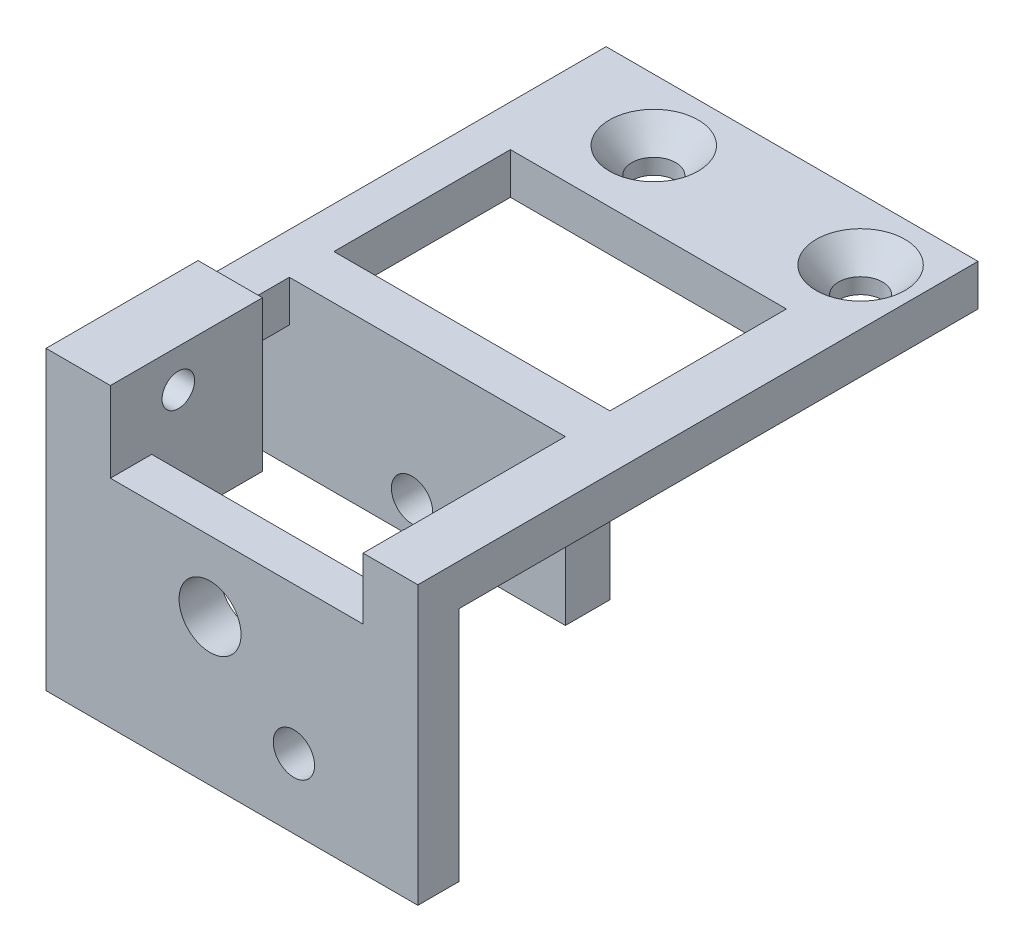
SolidWorks part; units mm, degrees
material "ABS"
ref_plane "Front Plane" through (0, 0, 0) normal (0, 0, 1) x (1, 0, 0)
ref_plane "Top Plane" through (0, 0, 0) normal (0, 1, 0) x (1, 0, 0)
ref_plane "Right Plane" through (0, 0, 0) normal (1, 0, 0) x (0, 0, -1)
sketch "Sketch1" plane through (0, 0, 0) normal (0, 0, 1) x (1, 0, 0)
  line L0 (0, 8.8442) -> (12.8921, -2.9343) construction
  line L1 (23.5226, 29.0697) -> (31.9421, 29.0697)
  line L2 (-25.2079, 8.8442) -> (-25.2079, -13.6023)
  line L3 (-25.2079, -13.6023) -> (31.9421, -13.6023)
  line L4 (31.9421, 29.0697) -> (31.9421, -13.6023)
  line L6 (-25.2079, 8.8442) -> (-25.2079, 31.9582)
  line L7 (-25.2079, 31.9582) -> (-18.8579, 31.9582)
  line L11 (23.5226, 22.6565) -> (23.5226, 29.0697)
  line L12 (-18.8579, 31.9582) -> (-15.3109, 31.9582)
  line L14 (-15.3109, 31.9582) -> (-15.3109, 22.6565)
  line L15 (-15.3109, 22.6565) -> (-15.3109, 19.6203)
  line L16 (-15.3109, 19.6203) -> (23.5226, 19.6203)
  line L17 (23.5226, 19.6203) -> (23.5226, 22.6565)
  circle A0 centre (12.8921, -2.9343) radius 3.175
  circle A1 centre (0, 8.8442) radius 4.7625
  dimension "D5" = 9.525
  dimension "D9" = 6.35
  dimension "D1" = 23.114
  dimension "D2" = 57.15
  dimension "D3" = 42.672
  dimension "D4" = 6.35
  dimension "D6" = 19.05
  dimension "D7" = 10.668
  dimension "D8" = 17.4625
extrude "Boss-Extrude1" add sketch "Sketch1" against normal blind 6.35
sketch "Sketch2" plane through (0, 0, 0) normal (0, 0, 1) x (1, 0, 0)
  line L0 (-25.2079, 31.9582) -> (-25.2079, -13.6023) construction
  line L1 (-18.8579, 31.9582) -> (-25.2079, 31.9582)
  line L3 (-18.8579, 8.8442) -> (-25.2079, 8.8442)
  line L4 (-25.2079, 31.9582) -> (-25.2079, 8.8442)
  line L6 (-15.3109, 31.9582) -> (-25.2079, 31.9582)
  line L7 (-15.3109, 31.9582) -> (-15.3109, 8.8442)
  line L8 (-15.3109, 8.8442) -> (-25.2079, 8.8442)
  line L9 (-25.2079, 31.9582) -> (-25.2079, 8.8442)
  line M4 (-15.3109, 31.9582) -> (-25.2079, 31.9582)
  line M5 (-25.2079, 31.9582) -> (-25.2079, -13.6023)
  line M15 (-15.3109, 19.6203) -> (-15.3109, 31.9582)
  dimension "D1" = 23.114
extrude "Boss-Extrude2" add sketch "Sketch2" against normal blind 23.368 contours L8 L7 L3 M15 M4 M5 region at (-20.2594, 20.4012, 0)
sketch "Sketch3" plane through (0, 29.0697, 0) normal (0, 1, 0) x (1, 0, 0)
  line L0 (-25.2079, 23.368) -> (-25.2079, 0) construction
  line L1 (-18.8579, 0) -> (-25.2079, 0)
  line L2 (-18.8579, 0) -> (-18.8579, 78.34)
  line L3 (-18.8579, 78.34) -> (-25.2079, 78.34)
  line L4 (-25.2079, 0) -> (-25.2079, 78.34)
  line L5 (31.9421, 0) -> (23.5601, 0)
  line L6 (31.9421, 0) -> (31.9421, 78.34)
  line L7 (31.9421, 78.34) -> (23.5601, 78.34)
  line L8 (23.5601, 0) -> (23.5601, 78.34)
  dimension "D2" = 8.382
  dimension "D3" = 78.34
  dimension "D4" = 78.34
extrude "Boss-Extrude3" add sketch "Sketch3" against normal blind 6.35
sketch "Sketch4" plane through (-25.2079, 0, 0) normal (-1, 0, 0) x (0, 0, 1)
  circle A0 centre (-10.4375, 26.1623) radius 2.5
  dimension "D1" = 5
extrude "Cut-Extrude1" cut sketch "Sketch4" against normal up to next
sketch "Sketch5" plane through (0, 29.0697, 0) normal (0, 1, 0) x (1, 0, 0)
  line L0 (31.9421, 78.34) -> (31.9421, 0) construction
  line L2 (-25.2079, 78.34) -> (-25.2079, 65.0226)
  line L3 (-25.2079, 65.0226) -> (31.9421, 65.0226)
  line L4 (31.9421, 78.34) -> (31.9421, 65.0226)
  line L5 (-25.2079, 78.34) -> (-25.2079, 23.368) construction
  line L9 (-25.2079, 78.34) -> (-25.2079, 86.0813)
  line L10 (-25.2079, 86.0813) -> (31.9421, 86.0813)
  line L11 (31.9421, 78.34) -> (31.9421, 86.0813)
extrude "Boss-Extrude4" add sketch "Sketch5" against normal blind 6.35
hole_wizard "CSK for 1/4 Flat Head Machine Screw1" positions "Sketch6" profile "Sketch7" countersink size "1/4" standard "ANSI Inch" end condition through all
sketch "Sketch6" plane through (0, 29.0697, 0) normal (0, 1, 0) x (1, 0, 0)
  point P0 (-8.3847, 76.5842)
  point P2 (23.3942, 76.5842)
  point P9 (0, 0)
  point P10 (-8.3847, 76.5842)
  point P11 (0, 0)
  point P12 (21.2851, 76.5842)
  point P13 (23.3942, 76.5842)
sketch "Sketch7" plane through (-8.3847, 29.0697, -76.5842) normal (1, 0, 0) x (0, 0, 1)
  line L0 (0, 0) -> (0, 42.672)
  line L1 (0, 42.672) -> (3.3782, 42.672)
  line L2 (3.3782, 42.672) -> (3.3782, 3.9592)
  line L3 (3.3782, 3.9592) -> (6.8199, 0)
  line L5 (6.8199, 0) -> (0, 0)
  line L6 (-3.3782, 3.9592) -> (-6.8199, 0) construction
  line L11 (0, -6.35) -> (0, 107.95) construction
  dimension "Thru Hole Dia." = 6.7564
  dimension "Thru Hole Depth" = 42.672
  dimension "Near C'Sink Dia." = 13.6398
  dimension "Near C'Sink Angle" = 82
sketch "Sketch8" plane through (0, 29.0697, 0) normal (0, 1, 0) x (1, 0, 0)
  line L0 (-25.2079, 86.0813) -> (-25.2079, 23.368) construction
  line L10 (-25.2079, 37.893) -> (23.5601, 37.893)
  line L11 (23.5601, 65.0226) -> (23.5601, 6.35) construction
  line L12 (23.5601, 37.893) -> (23.5601, 31.05)
  line L13 (23.5601, 31.05) -> (-25.2079, 31.05)
  line L14 (-25.2079, 37.893) -> (-25.2079, 31.05)
extrude "Boss-Extrude5" add sketch "Sketch8" against normal blind 25.146
sketch "Sketch10" plane through (0, 0, -37.893) normal (0, 0, -1) x (-1, 0, 0)
  circle A0 centre (0, 8.8442) radius 3.175
  dimension "D1" = 6.35
extrude "Cut-Extrude2" cut sketch "Sketch10" against normal up to next
